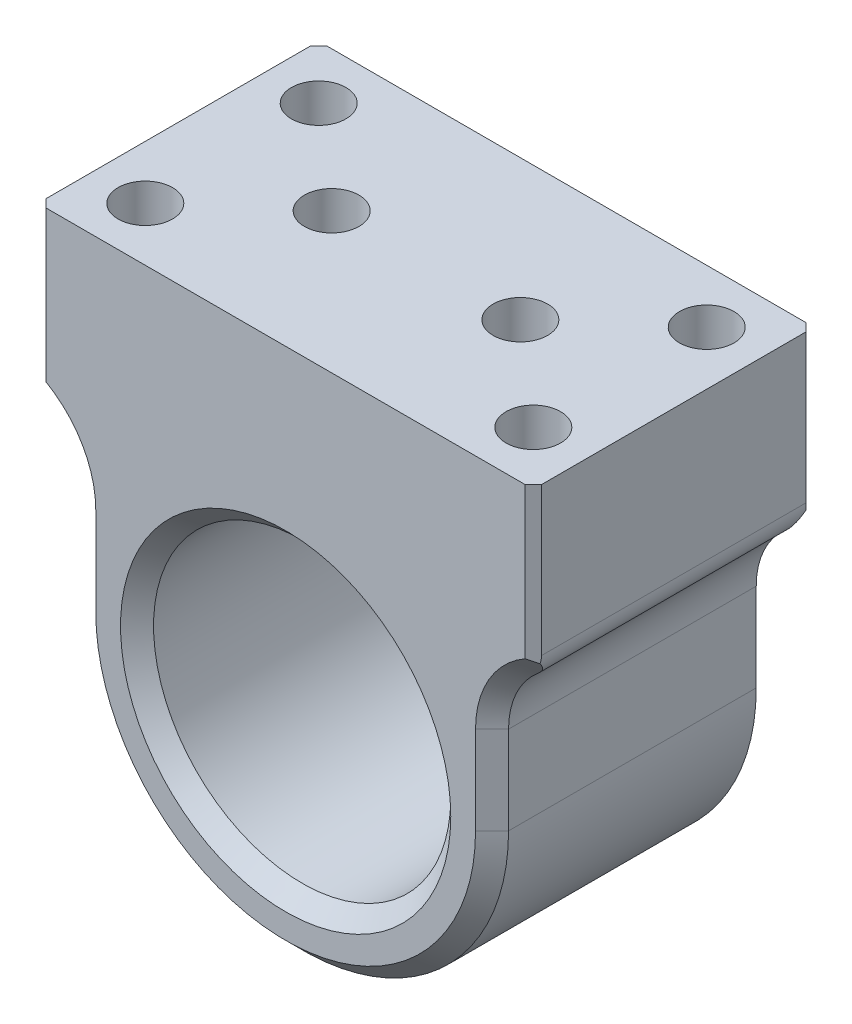
SolidWorks part; units mm, degrees
material "45#"
ref_plane "前视基准面" through (0, 0, 0) normal (0, 0, 1) x (1, 0, 0)
ref_plane "上视基准面" through (0, 0, 0) normal (0, 1, 0) x (1, 0, 0)
ref_plane "右视基准面" through (0, 0, 0) normal (1, 0, 0) x (0, 0, -1)
sketch "草图1" plane through (0, 0, 0) normal (0, 0, 1) x (1, 0, 0)
  line L2 (-16.5275, 348.6332) -> (-16.5275, 338.6332)
  line L5 (-46.5275, 348.6332) -> (-16.5275, 348.6332)
  line L8 (-46.5275, 348.6332) -> (-46.5275, 338.6332)
  line L9 (-46.5275, 338.6332) -> (-44.0275, 338.6332)
  line L10 (-44.0275, 328.9686) -> (-44.0275, 338.6332)
  line L11 (-19.0275, 328.9686) -> (-19.0275, 338.6332)
  line L12 (-19.0275, 338.6332) -> (-16.5275, 338.6332)
  circle A1 centre (-31.5275, 328.9686) radius 9
  arc A2 (-44.0275, 328.9686) -> (-19.0275, 328.9686) centre (-31.5275, 328.9686) ccw
  point P11 (-31.5275, 333.6332)
extrude "凸台-拉伸2" add sketch "草图1" along normal up to surface (17 mm away)
fillet "圆角7" radius 5 2 edges at (-19.0275, 338.6332, 8.5) (-44.0275, 338.6332, 8.5)
chamfer "倒角3" distance 1 angle 45 5 edges at (-18.3576, 336.8031, 17) (-19.0275, 331.6359, 17) (-44.6974, 336.8031, 17) (-31.5275, 316.4686, 17) (-44.0275, 331.6359, 17)
chamfer "倒角4" distance 1 angle 45 7 edges at (-44.6974, 336.8031, 0) (-18.3576, 336.8031, 0) (-44.0275, 331.6359, 0) (-19.0275, 331.6359, 0) (-31.5275, 316.4686, 0) (-22.5275, 328.9686, 17) (-22.5275, 328.9686, 0)
chamfer "倒角5" distance 0.5 angle 45 4 edges at (-16.5275, 344.1953, 0) (-16.5275, 344.1953, 17) (-46.5275, 344.1953, 0) (-46.5275, 344.1953, 17)
fillet "圆角9" radius 2 2 edges at (-16.5275, 338.6332, 8.5) (-46.5275, 338.6332, 8.5)
sketch "草图4" plane through (0, 348.6332, 0) normal (0, 1, 0) x (1, 0, 0)
  line L5 (-46.2775, -0.2483) -> (-46.2775, -16.75)
  line L14 (-46.5275, -16.5) -> (-46.0275, -17) construction
  line L15 (-46.2775, -16.75) -> (-16.7775, -16.75)
  line L16 (-17.0275, -17) -> (-16.5275, -16.5) construction
  line L17 (-16.7775, -16.75) -> (-16.7775, -0.2483)
  line L19 (-16.7775, -0.2483) -> (-46.2775, -0.2483)
  line L20 (-31.5275, -0.2483) -> (-31.5275, -16.75) construction
  circle A0 centre (-43.2775, -13.75) radius 3
  circle A1 centre (-43.2775, -3.2483) radius 3
  circle A2 centre (-19.7775, -3.2483) radius 3
  circle A3 centre (-19.7775, -13.75) radius 3
  point P22 (-31.5275, -8.4991)
hole_wizard "M4 螺纹孔3" positions "草图9" profile "草图10" tap size "M4" standard "GB"
sketch "草图9" plane through (0, 348.6332, 0) normal (0, 1, 0) x (1, 0, 0)
  point P6 (-19.7775, -13.75)
  point P8 (-43.2775, -13.75)
  point P19 (-43.2775, -3.2483)
  point P21 (-19.7775, -3.2483)
sketch "草图10" plane through (-19.7775, 348.6332, 13.75) normal (1, 0, 0) x (0, 0, 1)
  line L0 (0, 0) -> (0, 11.0914)
  line L1 (0, 11.0914) -> (1.65, 10.1)
  line L2 (1.65, 10.1) -> (1.65, 0)
  line L5 (1.65, 0) -> (0, 0)
  line L10 (0, 11.0914) -> (-1.65, 10.1) construction
  line L11 (0, -6.35) -> (0, 107.95) construction
  dimension "螺纹孔钻头直径" = 3.3
  dimension "螺纹孔钻头深度" = 10.1
  dimension "导头角度" = 118
cosmetic thread "孔螺蚊线8" parameters "D1"=8, "D2"=4
cosmetic thread "孔螺蚊线9" parameters "D1"=8, "D2"=4
cosmetic thread "孔螺蚊线10" parameters "D1"=8, "D2"=4
cosmetic thread "孔螺蚊线11" parameters "D1"=8, "D2"=4
sketch "草图12" plane through (0, 348.6332, 0) normal (0, 1, 0) x (1, 0, 0)
  circle A0 centre (-25.8131, -8.4991) radius 8
  circle A1 centre (-37.2419, -8.4991) radius 8
hole_wizard "M4 螺纹孔4" positions "草图13" profile "草图14" tap size "M4" standard "GB"
sketch "草图13" plane through (0, 348.6332, 0) normal (0, 1, 0) x (1, 0, 0)
  point P0 (-37.2419, -8.4991)
  point P2 (-25.8131, -8.4991)
sketch "草图14" plane through (-37.2419, 348.6332, 8.4991) normal (1, 0, 0) x (0, 0, 1)
  line L0 (0, 0) -> (0, 8.9914)
  line L1 (0, 8.9914) -> (1.65, 8)
  line L2 (1.65, 8) -> (1.65, 0)
  line L5 (1.65, 0) -> (0, 0)
  line L10 (0, 8.9914) -> (-1.65, 8) construction
  line L11 (0, -6.35) -> (0, 107.95) construction
  dimension "螺纹孔钻头直径" = 3.3
  dimension "螺纹孔钻头深度" = 8
  dimension "导头角度" = 118
cosmetic thread "孔螺蚊线12" parameters "D1"=8, "D2"=4
cosmetic thread "孔螺蚊线13" parameters "D1"=8, "D2"=4
